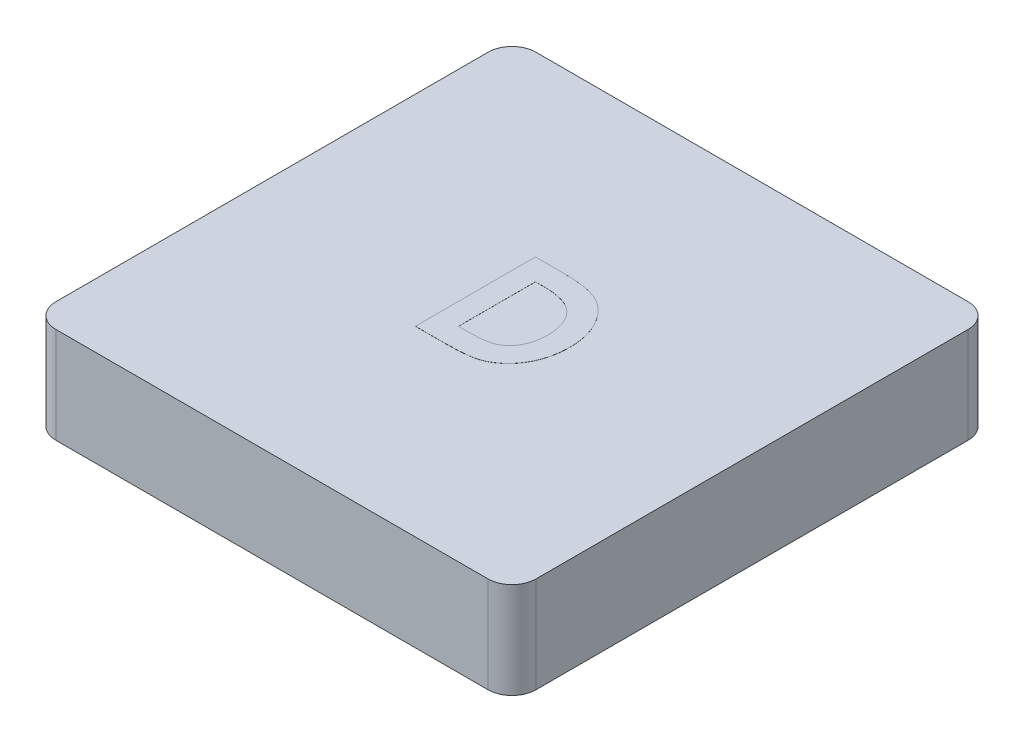
SolidWorks part; units mm, degrees
ref_plane "Front Plane" through (0, 0, 0) normal (0, 0, 1) x (1, 0, 0)
ref_plane "Top Plane" through (0, 0, 0) normal (0, 1, 0) x (1, 0, 0)
ref_plane "Right Plane" through (0, 0, 0) normal (1, 0, 0) x (0, 0, -1)
sketch "Sketch1" plane through (0, 0, 0) normal (0, 1, 0) x (1, 0, 0)
  line L0 (0, 0) -> (12.7, 0)
  line L1 (12.7, 0) -> (12.7, 12.7)
  line L2 (12.7, 12.7) -> (0, 12.7)
  line L3 (0, 12.7) -> (0, 0)
  dimension "D1" = 12.7
  dimension "D2" = 12.7
extrude "Boss-Extrude1" add sketch "Sketch1" along normal blind 2.54
fillet "Fillet1" radius 0.635 4 edges at (0, 1.27, -12.7) (12.7, 1.27, -12.7) (12.7, 1.27, 0) (0, 1.27, 0)
shell "Shell1" thickness 0.635 removed face at (6.35, 0, -6.35)
sketch "Sketch2" plane through (0, 1.905, 0) normal (0, -1, 0) x (-1, 0, 0)
  line L0 (-0.635, 6.35) -> (-12.065, 6.35) construction
  line L1 (-0.635, 12.065) -> (-0.635, 0.635) construction
  line L2 (-12.065, 0.635) -> (-12.065, 12.065) construction
  line L3 (-6.35, 0.635) -> (-6.35, 12.065) construction
  line L4 (-0.635, 0.635) -> (-12.065, 0.635) construction
  line L5 (-12.065, 12.065) -> (-0.635, 12.065) construction
  circle A0 centre (-6.35, 6.35) radius 2.54
  dimension "D1" = 5.08
extrude "Boss-Extrude2" add sketch "Sketch2" along normal up to surface (1.905 mm away) up to face at (6.35, 0, -6.35)
sketch "Sketch3" plane through (0, 2.54, 0) normal (0, 1, 0) x (1, 0, 0)
  line L0 (0, 12.065) -> (0, 0.635) construction
  line L1 (0.635, 0) -> (12.065, 0) construction
  text T0 "<b>D</b>"
  point P1 (0, 0)
  dimension "D1" = 4.953
  dimension "D2" = 4.826
extrude "Boss-Extrude3" add sketch "Sketch3" along normal blind 0.0025
